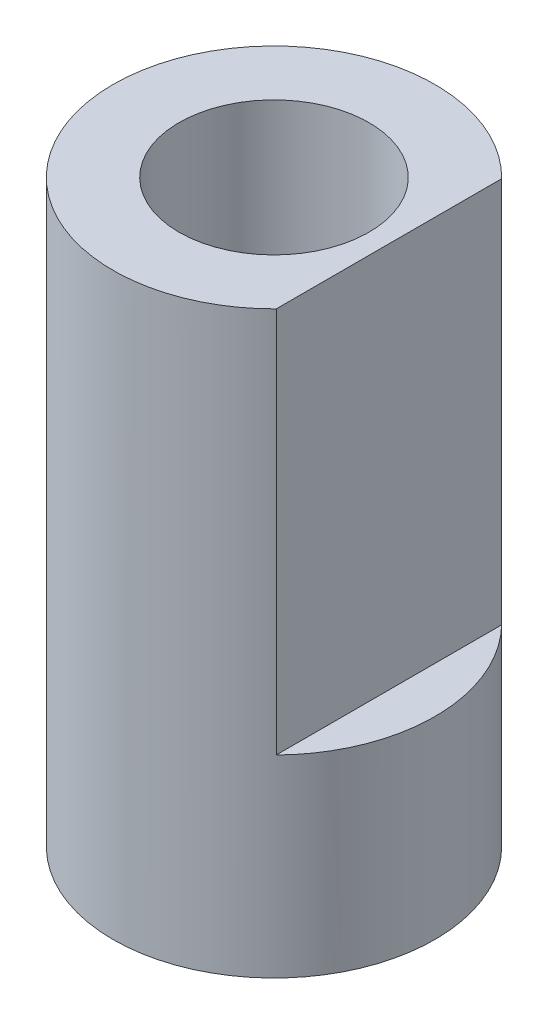
SolidWorks part; units mm, degrees
ref_plane "Front Plane" through (0, 0, 0) normal (0, 0, 1) x (1, 0, 0)
ref_plane "Top Plane" through (0, 0, 0) normal (0, 1, 0) x (1, 0, 0)
ref_plane "Right Plane" through (0, 0, 0) normal (1, 0, 0) x (0, 0, -1)
sketch "Sketch1" plane through (0, 0, 0) normal (0, 1, 0) x (1, 0, 0)
  line L0 (1.7854, -1.75) -> (1.7854, 1.75)
  circle A0 centre (0, 0) radius 1.475
  circle A1 centre (0, 0) radius 2.5
  dimension "D1" = 2.95
  dimension "D2" = 5
  dimension "D3" = 3.5
extrude "Boss-Extrude4" add sketch "Sketch1" along normal blind 3 contours L0 A1 A0 | L0 A1 region at (-2.4341, 0, 0) region at (2.075, 0, 0)
extrude "Boss-Extrude5" add sketch "Sketch1<3>" along normal blind 6 from surface contours L0 A1 A0 region at (-2.4341, 0, 0) starting at face at (0, 3, 1.475)
sketch "Sketch1<3>" plane through (0, 0, 0) normal (0, 1, 0) x (1, 0, 0) same geometry as "Sketch1"
